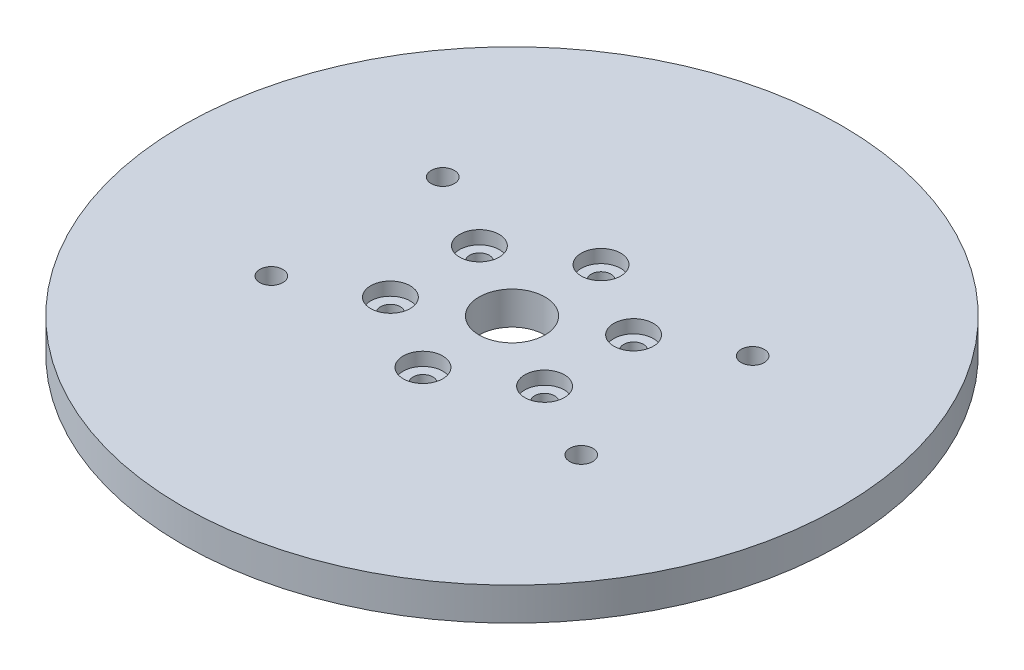
SolidWorks part; units mm, degrees
ref_plane "Front" through (0, 0, 0) normal (0, 0, 1) x (1, 0, 0)
ref_plane "Top" through (0, 0, 0) normal (0, 1, 0) x (1, 0, 0)
ref_plane "Right" through (0, 0, 0) normal (1, 0, 0) x (0, 0, -1)
sketch "Эскиз1" plane through (0, 0, 0) normal (0, 1, 0) x (1, 0, 0)
  line L0 (0, 50) -> (0, -50) construction
  line L1 (-50, 0) -> (50, 0) construction
  circle A0 centre (-23.5, 13) radius 1.75
  circle A1 centre (-23.5, -13) radius 1.75
  circle A2 centre (0, 0) radius 5
  circle A3 centre (0, 0) radius 50
  circle A4 centre (23.5, -13) radius 1.75
  circle A5 centre (23.5, 13) radius 1.75
  dimension "D1" = 10
  dimension "D2" = 3.5
  dimension "D5" = 100
  dimension "D3" = 26
  dimension "D4" = 23.5
extrude "Бобышка-Вытянуть1" add sketch "Эскиз1" along normal blind 5
sketch "Эскиз2" plane through (0, 0, 0) normal (0, -1, 0) x (1, 0, 0)
  line L1 (-25.2321, 16) -> (-26.9641, 13)
  line L2 (-26.9641, 13) -> (-25.2321, 10)
  line L3 (-25.2321, 10) -> (-21.7679, 10)
  line L4 (-21.7679, 10) -> (-20.0359, 13)
  line L5 (-20.0359, 13) -> (-21.7679, 16)
  line L6 (-21.7679, 16) -> (-25.2321, 16)
  line L7 (21.7679, 16) -> (20.0359, 13)
  line L8 (20.0359, 13) -> (21.7679, 10)
  line L9 (21.7679, 10) -> (25.2321, 10)
  line L10 (25.2321, 10) -> (26.9641, 13)
  line L11 (26.9641, 13) -> (25.2321, 16)
  line L12 (25.2321, 16) -> (21.7679, 16)
  line L13 (21.7679, -10) -> (20.0359, -13)
  line L14 (20.0359, -13) -> (21.7679, -16)
  line L15 (21.7679, -16) -> (25.2321, -16)
  line L16 (25.2321, -16) -> (26.9641, -13)
  line L17 (26.9641, -13) -> (25.2321, -10)
  line L18 (25.2321, -10) -> (21.7679, -10)
  line L19 (-25.2321, -10) -> (-26.9641, -13)
  line L20 (-26.9641, -13) -> (-25.2321, -16)
  line L21 (-25.2321, -16) -> (-21.7679, -16)
  line L22 (-21.7679, -16) -> (-20.0359, -13)
  line L23 (-20.0359, -13) -> (-21.7679, -10)
  line L24 (-21.7679, -10) -> (-25.2321, -10)
  circle A0 centre (-23.5, 13) radius 3 construction
  circle A1 centre (23.5, 13) radius 3 construction
  circle A2 centre (23.5, -13) radius 3 construction
  circle A3 centre (-23.5, -13) radius 3 construction
  circle A4 centre (0, 13.5) radius 1.5
  circle A5 centre (11.6913, 6.75) radius 1.5
  circle A6 centre (11.6913, -6.75) radius 1.5
  circle A7 centre (0, -13.5) radius 1.5
  circle A8 centre (-11.6913, -6.75) radius 1.5
  circle A9 centre (-11.6913, 6.75) radius 1.5
  point P51 (0, 0)
  dimension "D1" = 6
  dimension "D2" = 3
  dimension "D3" = 13.5
  dimension "D4" = 6
extrude "Вырез-Вытянуть1" cut sketch "Эскиз2" against normal blind 2
sketch "Эскиз3" plane through (0, 0, 0) normal (0, 0, 1) x (1, 0, 0)
  line L0 (-50, 0) -> (50, 0) construction
  line L1 (-50, 0) -> (50, 0)
  line L2 (0, 0) -> (0, -17.5167) construction
  circle A0 centre (-45, -1.5) radius 3
  dimension "D1" = 6
  dimension "D2" = 45
  dimension "D3" = 1.5
revolve "Вырез-Повернуть1" cut sketch "Эскиз3" angle 360 about L2 region at (-45, 0.6151, 0) region at (-45, -2.014, 0)
extrude "Вырез-Вытянуть2" cut sketch "Эскиз2<3>" against normal through all both and the other way through all contours A7 | A8 | A9 | A6 | A4 | A5 region at (0, 0, 13.5) region at (11.6913, 0, -6.75) region at (0, 0, -13.5) region at (-11.6913, 0, -6.75) region at (-11.6913, 0, 6.75)
sketch "Эскиз2<3>" plane through (0, 0, 0) normal (0, -1, 0) x (1, 0, 0) same geometry as "Эскиз2"
sketch "Эскиз4" plane through (0, 5, 0) normal (0, 1, 0) x (1, 0, 0)
  circle A0 centre (0, 13.5) radius 1.5 construction
  circle A1 centre (0, 13.5) radius 1.5
  circle A2 centre (-11.6913, 6.75) radius 1.5 construction
  circle A3 centre (-11.6913, 6.75) radius 1.5
  circle A4 centre (-23.5, -13) radius 1.75 construction
  circle A5 centre (-23.5, -13) radius 1.75
  circle A6 centre (-11.6913, 6.75) radius 3
  circle A7 centre (0, 13.5) radius 3
  circle A8 centre (11.6913, 6.75) radius 3
  circle A9 centre (11.6913, -6.75) radius 3
  circle A10 centre (0, -13.5) radius 3
  circle A11 centre (-11.6913, -6.75) radius 3
  point P22 (0, 0)
  dimension "D1" = 6
  dimension "D2" = 6
extrude "Вырез-Вытянуть3" cut sketch "Эскиз4" against normal blind 2
